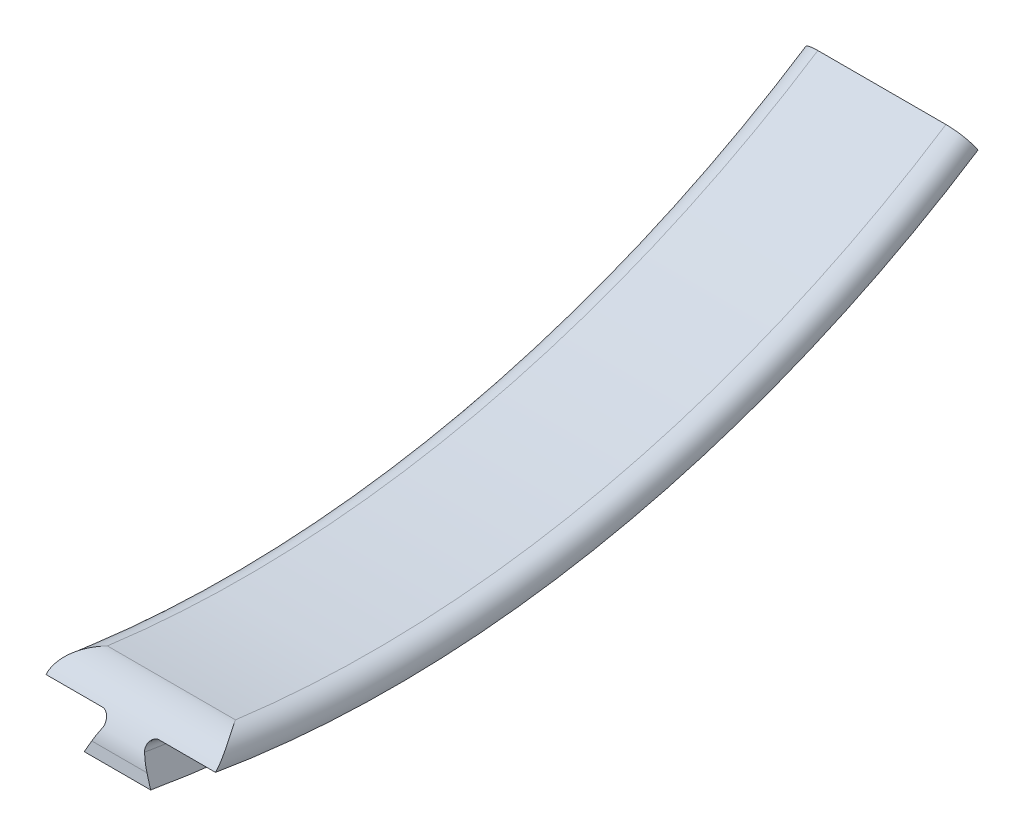
SolidWorks part; units mm, degrees
ref_plane "Front Plane" through (0, 0, 0) normal (0, 0, 1) x (1, 0, 0)
ref_plane "Top Plane" through (0, 0, 0) normal (0, 1, 0) x (1, 0, 0)
ref_plane "Right Plane" through (0, 0, 0) normal (1, 0, 0) x (0, 0, -1)
sketch "Sketch1" plane through (0, 0, 0) normal (0, 0, -1) x (1, 0, 0)
  line L0 (-3.6406, 46) -> (-1.2177, 46)
  line L1 (-0.875, 46) -> (-1.75, 47.75) construction
  line L2 (-1.75, 47.75) -> (1.75, 47.75) construction
  line L3 (1.75, 47.75) -> (0.875, 46) construction
  line L4 (1.2177, 46) -> (3.6406, 46)
  line L5 (-0.875, 46) -> (0.875, 46) construction
  line L6 (0, 46) -> (0, 47.75) construction
  line L7 (-3.6406, 46) -> (-3.6406, 44.6758) construction
  line L8 (-2.75, 45.1094) -> (2.75, 45.1094)
  line L9 (0, 0) -> (0, 45.1094) construction
  line L10 (0, 46) -> (0, 45.1094) construction
  line L11 (-0.9047, 46.5065) -> (-1.4264, 47.55)
  line L12 (-1.4264, 47.55) -> (1.4264, 47.55)
  line L13 (1.4264, 47.55) -> (0.9047, 46.5065)
  line L14 (1.4264, 47.55) -> (0.6961, 46.0894) construction
  line L15 (-0.6961, 46.0894) -> (-1.4264, 47.55) construction
  line L16 (1.2368, 46.7236) -> (0, 46.7236) construction
  line L17 (0, 46.7236) -> (-1.2368, 46.7236) construction
  line L18 (0, 0) -> (87.3462, 0) construction
  arc A0 (1.2177, 46) -> (0.9047, 46.5065) centre (1.2177, 46.35) cw
  arc A1 (-1.2177, 46) -> (-0.9047, 46.5065) centre (-1.2177, 46.35) ccw
  arc A2 (-3.6406, 46) -> (-2.75, 45.1094) centre (-2.75, 46) ccw
  arc A3 (2.75, 45.1094) -> (3.6406, 46) centre (2.75, 46) ccw
  arc A4 (1.2368, 46.7236) -> (1.684, 46) centre (1.684, 46.5) ccw construction
  point P10 (0, 0)
  dimension "D6" = 0.8906
  dimension "D9" = 0.5
  dimension "D10" = 0.35
  dimension "D1" = 1.75
  dimension "D2" = 3.5
  dimension "D3" = 1.75
  dimension "D4" = 45.1094
  dimension "D5" = 0.2
  dimension "D7" = 5.5
  dimension "D8" = 0.8906
  dimension "D11" = 26.565
revolve "Revolve1" add sketch "Sketch1" angle 33 about L18
fillet "Fillet1" radius 2 1 edges at (0, -44.4241, 7.8332)
